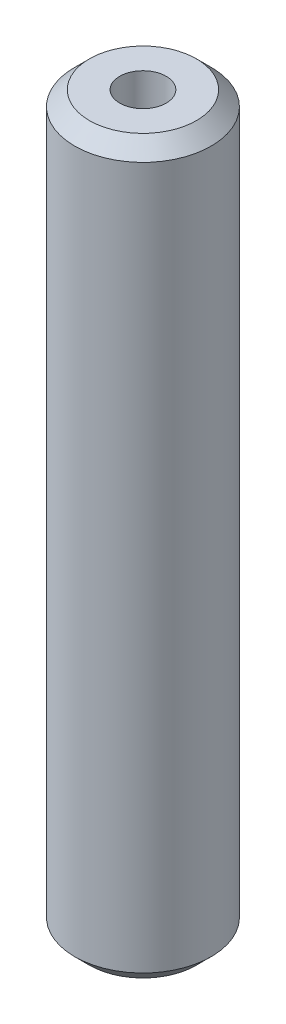
SolidWorks part; units mm, degrees
ref_plane "Front Plane" through (0, 0, 0) normal (0, 0, 1) x (1, 0, 0)
ref_plane "Top Plane" through (0, 0, 0) normal (0, 1, 0) x (1, 0, 0)
ref_plane "Right Plane" through (0, 0, 0) normal (1, 0, 0) x (0, 0, -1)
sketch "Sketch1" plane through (0, 0, 0) normal (0, 1, 0) x (1, 0, 0)
  circle A0 centre (0, 0) radius 10
  dimension "SHAFT_OD" = 20
extrude "Boss-Extrude1" add sketch "Sketch1" along normal blind 107.1851
sketch "Sketch2" plane through (0, 0, 0) normal (0, 1, 0) x (1, 0, 0)
  circle A0 centre (0, 0) radius 3.4094
  dimension "BORE_D" = 6.8188
extrude "Cut-Extrude1" cut sketch "Sketch2" along normal through all
chamfer "Chamfer1" distance 2.1574 angle 45 2 edges at (0, 107.1851, 10) (0, 0, 10)
